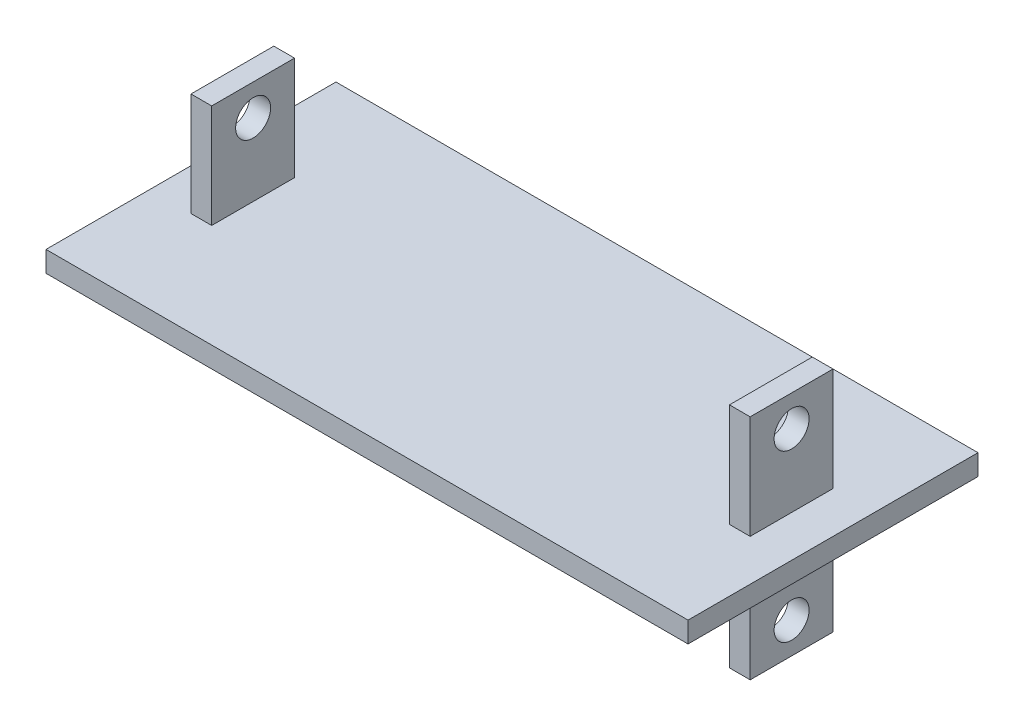
SolidWorks part; units mm, degrees
ref_plane "Front Plane" through (0, 0, 0) normal (0, 0, 1) x (1, 0, 0)
ref_plane "Top Plane" through (0, 0, 0) normal (0, 1, 0) x (1, 0, 0)
ref_plane "Right Plane" through (0, 0, 0) normal (1, 0, 0) x (0, 0, -1)
sketch "Sketch1" plane through (0, 0, 0) normal (0, 1, 0) x (1, 0, 0)
  line L0 (-89.5777, 0) -> (113.3723, 0) construction
  line L1 (98.425, -44.45) -> (-98.425, -44.45)
  line L2 (98.425, -44.45) -> (98.425, 44.45)
  line L3 (98.425, 44.45) -> (-98.425, 44.45)
  line L4 (-98.425, -44.45) -> (-98.425, 44.45)
  line L5 (98.425, -44.45) -> (-98.425, 44.45) construction
  line L6 (98.425, 44.45) -> (-98.425, -44.45) construction
  line L7 (-79.375, -12.7) -> (-85.725, -12.7)
  line L8 (-79.375, -12.7) -> (-79.375, 12.7)
  line L9 (-79.375, 12.7) -> (-85.725, 12.7)
  line L10 (-85.725, -12.7) -> (-85.725, 12.7)
  line L11 (-79.375, -12.7) -> (-85.725, 12.7) construction
  line L12 (-79.375, 12.7) -> (-85.725, -12.7) construction
  line L13 (79.375, -12.7) -> (85.725, -12.7)
  line L14 (79.375, -12.7) -> (79.375, 12.7)
  line L15 (79.375, 12.7) -> (85.725, 12.7)
  line L16 (85.725, -12.7) -> (85.725, 12.7)
  line L17 (79.375, -12.7) -> (85.725, 12.7) construction
  line L18 (79.375, 12.7) -> (85.725, -12.7) construction
  point P0 (0, 0)
  point P6 (-82.55, 0)
  point P11 (82.55, 0)
  point P21 (-98.425, 0)
  dimension "D1" = 196.85
  dimension "D2" = 88.9
  dimension "D4" = 6.35
  dimension "D3" = 12.7
  dimension "D5" = 12.7
  dimension "D6" = 25.4
extrude "Boss-Extrude1" add sketch "Sketch1" along normal mid plane 6.35 contours L10 L7 L8 L9 | L13 L16 L15 L14 | L4 L1 L2 L3 L16 L13 L14 L15 L7 L10 L9 L8 region at (0, 0, 0) region at (-82.55, 0, 0) region at (82.55, 0, 0)
extrude "Boss-Extrude2" add sketch "Sketch1<3>" along normal mid plane 69.85 contours L10 L7 L8 L9 | L13 L16 L15 L14 region at (-82.55, 0, 0) region at (82.55, 0, 0)
sketch "Sketch1<3>" plane through (0, 0, 0) normal (0, 1, 0) x (1, 0, 0) same geometry as "Sketch1"
sketch "Sketch2" plane through (85.725, 0, 0) normal (1, 0, 0) x (0, 0, -1)
  line L0 (0, 25.4) -> (0, -25.4) construction
  circle A0 centre (0, 25.4) radius 5.3578
  circle A1 centre (0, -25.4) radius 5.3578
  point P3 (0, 0)
  dimension "D2" = 10.7156
  dimension "D1" = 50.8
extrude "Cut-Extrude1" cut sketch "Sketch2" against normal through all both and the other way through all
equation "\"Coupler_OD\" = 3.899in"
equation "\"Coupler_ID\" = 3.755in"
equation "\"Mid_Coupler_Length\" = 8in"
equation "\"Lead_Screw_Hole_Diam\" = (27/64)*1in"
equation "\"Lead_Screw_Dist\" = 2in"
equation "\"Avionics_Bay_Width\"= 3.5in"
equation "\"D1@Sketch1\"=\"Mid_Coupler_Length\"-0.25"
equation "\"D2@Sketch1\"=\"Avionics_Bay_Width\""
equation "\"Board_Thickness\"= 0.25in"
equation "\"D4@Sketch1\"=\"Board_Thickness\""
equation "\"D1@Boss-Extrude1\"=\"Board_Thickness\""
equation "\"D1@Sketch2\"=\"Lead_Screw_Dist\""
equation "\"D2@Sketch2\"=\"Lead_Screw_Hole_Diam\""
equation "\"Stickout_Width\"= 2.75"
equation "\"D1@Boss-Extrude2\"=\"Stickout_Width\""
